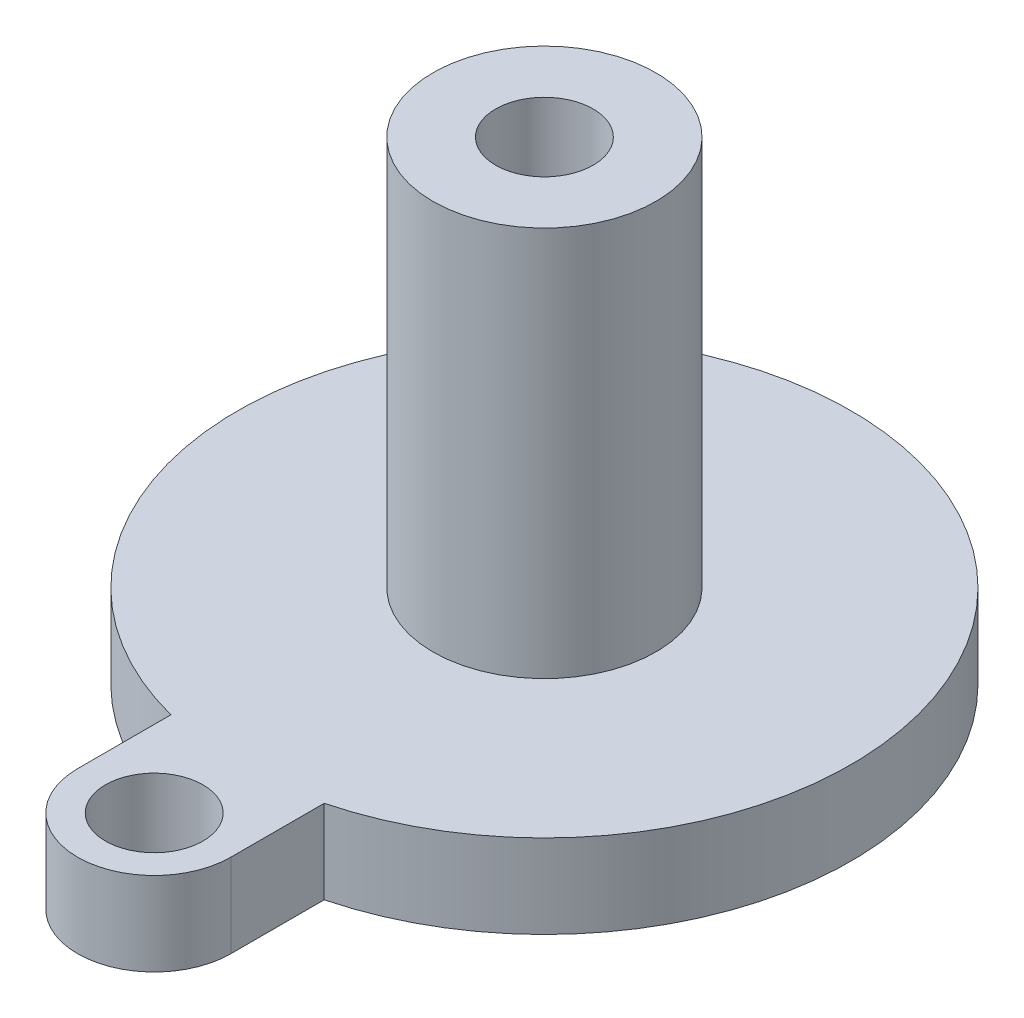
SolidWorks part; units mm, degrees
ref_plane "Front Plane" through (0, 0, 0) normal (0, 0, 1) x (1, 0, 0)
ref_plane "Top Plane" through (0, 0, 0) normal (0, 1, 0) x (1, 0, 0)
ref_plane "Right Plane" through (0, 0, 0) normal (1, 0, 0) x (0, 0, -1)
sketch "Sketch1" plane through (0, 0, 0) normal (0, 1, 0) x (1, 0, 0)
  circle A0 centre (0, 0) radius 11
extrude "Boss-Extrude1" add sketch "Sketch1" along normal blind 3
sketch "Sketch2" plane through (0, 3, 0) normal (0, 1, 0) x (1, 0, 0)
  circle A0 centre (0, 0) radius 4
extrude "Boss-Extrude2" add sketch "Sketch2" along normal blind 14
sketch "Sketch3" plane through (0, 17, 0) normal (0, 1, 0) x (1, 0, 0)
  circle A0 centre (0, 0) radius 1.75
extrude "Cut-Extrude1" cut sketch "Sketch3" against normal blind 20
sketch "Sketch4" plane through (0, 0, 0) normal (0, -1, 0) x (1, 0, 0)
  line L0 (-2.75, 14) -> (-2.75, 10.6507)
  line L1 (2.75, 14) -> (2.75, 10.6507)
  circle A0 centre (0, 14) radius 1.75
  circle A1 centre (0, 14) radius 2.75
  circle A2 centre (0, 0) radius 11 construction
  arc A3 (-2.75, 10.6507) -> (2.75, 10.6507) centre (0, 0) cw
  circle M2 centre (0, 0) radius 11
  dimension "D1" = 14
extrude "Boss-Extrude3" add sketch "Sketch4" against normal blind 3 contours A1 L0 L1 M2 | A1 A0 region at (0, 0, 11.1856) region at (0, 0, 16.6722)
